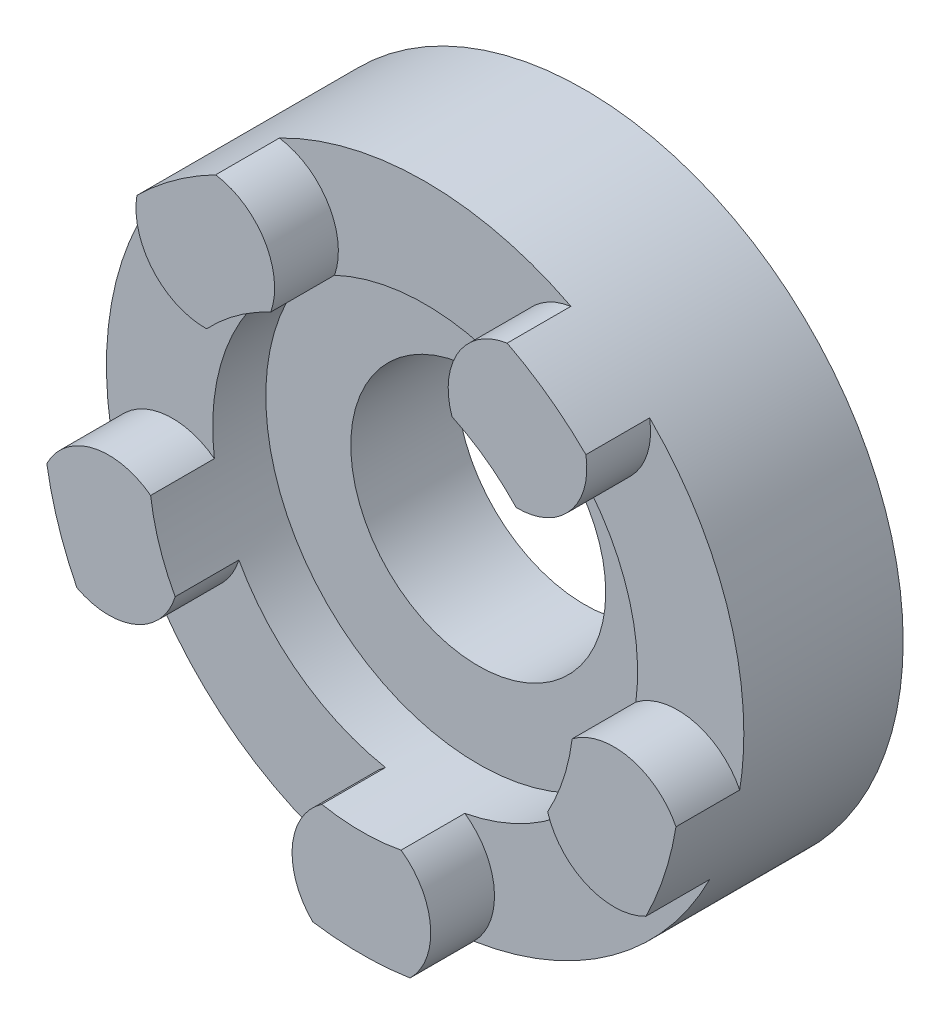
SolidWorks part; units mm, degrees
ref_plane "Front Plane" through (0, 0, 0) normal (0, 0, 1) x (1, 0, 0)
ref_plane "Top Plane" through (0, 0, 0) normal (0, 1, 0) x (1, 0, 0)
ref_plane "Right Plane" through (0, 0, 0) normal (1, 0, 0) x (0, 0, -1)
sketch "Sketch1" plane through (0, 0, 0) normal (0, 0, 1) x (1, 0, 0)
  circle A0 centre (0, 0) radius 10
  circle A1 centre (0, 0) radius 15
  circle A2 centre (0, 0) radius 6
extrude "Boss-Extrude1" add sketch "Sketch1" against normal blind 5 contours A1 A0 | A0 A2 region at (-9.7172, 0, 0) region at (-14.5757, 0, 0)
sketch "Sketch2" plane through (0, 0, 0) normal (0, 0, 1) x (1, 0, 0)
  circle A0 centre (0, 0) radius 10
  circle A1 centre (0, 0) radius 15
extrude "Boss-Extrude2" add sketch "Sketch2" along normal blind 2.5
sketch "Sketch3" plane through (0, 0, 2.5) normal (0, 0, 1) x (1, 0, 0)
  line L0 (0, 0) -> (0, -15) construction
  circle A0 centre (0, 0) radius 15 construction
  arc A1 (-2.2906, -14.8241) -> (2.2906, -14.8241) centre (0, 0) ccw
  arc A2 (-1.8675, -9.8241) -> (1.8675, -9.8241) centre (0, 0) ccw
  arc A5 (3.2352, -12.0741) -> (2.2906, -14.8241) centre (0, -12.5) cw
  arc A6 (3.2352, -12.0741) -> (1.8675, -9.8241) centre (0, -12.5) ccw
  arc A7 (-3.2352, -12.0741) -> (-2.2906, -14.8241) centre (0, -12.5) ccw
  arc A8 (-3.2352, -12.0741) -> (-1.8675, -9.8241) centre (0, -12.5) cw
  arc A37 (-14.8064, -2.4024) -> (-13.3907, -6.7594) centre (0, 0) ccw
  arc A38 (-9.9203, -1.2597) -> (-8.7662, -4.8119) centre (0, 0) ccw
  arc A39 (-10.4834, -6.808) -> (-13.3907, -6.7594) centre (-11.8882, -3.8627) cw
  arc A40 (-10.4834, -6.808) -> (-8.7662, -4.8119) centre (-11.8882, -3.8627) ccw
  arc A41 (-12.4829, -0.6542) -> (-14.8064, -2.4024) centre (-11.8882, -3.8627) ccw
  arc A42 (-12.4829, -0.6542) -> (-9.9203, -1.2597) centre (-11.8882, -3.8627) cw
  arc A43 (-6.8602, 13.3393) -> (-10.5665, 10.6465) centre (0, 0) ccw
  arc A44 (-4.2636, 9.0455) -> (-7.2853, 6.8501) centre (0, 0) ccw
  arc A45 (-9.7143, 7.8665) -> (-10.5665, 10.6465) centre (-7.3473, 10.1127) cw
  arc A46 (-9.7143, 7.8665) -> (-7.2853, 6.8501) centre (-7.3473, 10.1127) ccw
  arc A47 (-4.4796, 11.6698) -> (-6.8602, 13.3393) centre (-7.3473, 10.1127) ccw
  arc A48 (-4.4796, 11.6698) -> (-4.2636, 9.0455) centre (-7.3473, 10.1127) cw
  arc A49 (10.5665, 10.6465) -> (6.8602, 13.3393) centre (0, 0) ccw
  arc A50 (7.2853, 6.8501) -> (4.2636, 9.0455) centre (0, 0) ccw
  arc A51 (4.4796, 11.6698) -> (6.8602, 13.3393) centre (7.3473, 10.1127) cw
  arc A52 (4.4796, 11.6698) -> (4.2636, 9.0455) centre (7.3473, 10.1127) ccw
  arc A53 (9.7143, 7.8665) -> (10.5665, 10.6465) centre (7.3473, 10.1127) ccw
  arc A54 (9.7143, 7.8665) -> (7.2853, 6.8501) centre (7.3473, 10.1127) cw
  arc A55 (13.3907, -6.7594) -> (14.8064, -2.4024) centre (0, 0) ccw
  arc A56 (8.7662, -4.8119) -> (9.9203, -1.2597) centre (0, 0) ccw
  arc A57 (12.4829, -0.6542) -> (14.8064, -2.4024) centre (11.8882, -3.8627) cw
  arc A58 (12.4829, -0.6542) -> (9.9203, -1.2597) centre (11.8882, -3.8627) ccw
  arc A59 (10.4834, -6.808) -> (13.3907, -6.7594) centre (11.8882, -3.8627) ccw
  arc A60 (10.4834, -6.808) -> (8.7662, -4.8119) centre (11.8882, -3.8627) cw
  point P12 (3.2352, -12.0741)
  point P15 (-3.2352, -12.0741)
  point P21 (-10.4834, -6.808)
  point P24 (-12.4829, -0.6542)
  point P31 (-9.7143, 7.8665)
  point P33 (-4.4796, 11.6698)
  point P40 (4.4796, 11.6698)
  point P42 (9.7143, 7.8665)
  point P49 (12.4829, -0.6542)
  point P51 (10.4834, -6.808)
  dimension "D1" = 5
extrude "Boss-Extrude4" add sketch "Sketch3" along normal blind 3
